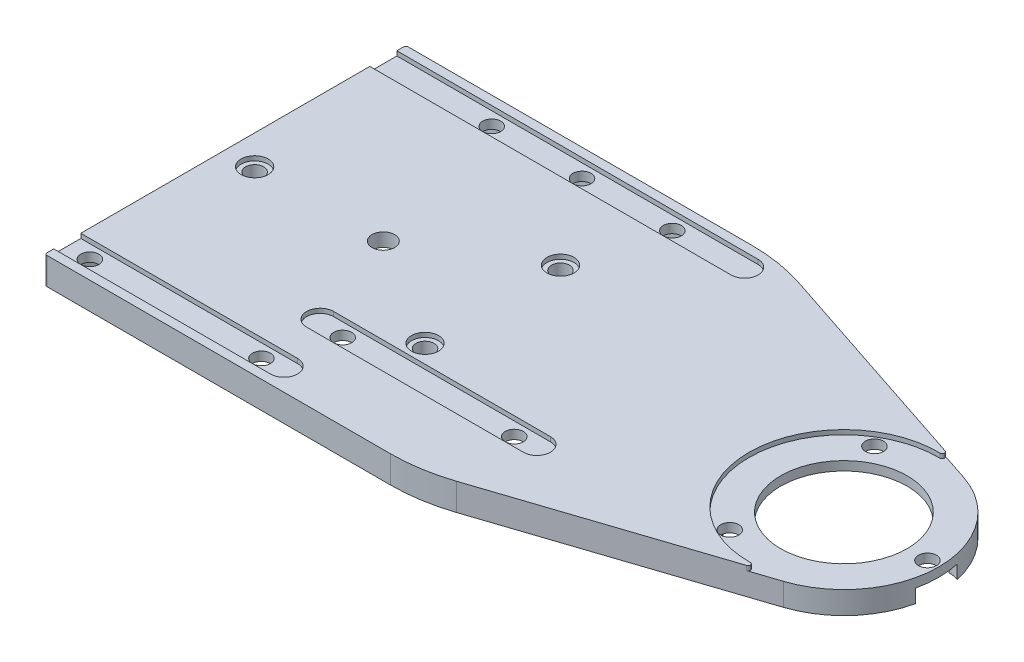
SolidWorks part; units mm, degrees
ref_plane "前视基准面" through (0, 0, 0) normal (0, 0, 1) x (1, 0, 0)
ref_plane "上视基准面" through (0, 0, 0) normal (0, 1, 0) x (1, 0, 0)
ref_plane "右视基准面" through (0, 0, 0) normal (1, 0, 0) x (0, 0, -1)
sketch "草图1" plane through (0, 0, 0) normal (0, 1, 0) x (1, 0, 0)
  line L0 (-20.9942, 0) -> (181.0483, 0) construction
  line L1 (-13, 40) -> (70, 40)
  line L2 (-13, 40) -> (-13, -40)
  line L3 (-13, -40) -> (70, -40)
  line L4 (70, 40) -> (130.6005, 19.9357)
  line L5 (0, 42.5732) -> (0, -49.2392) construction
  line L6 (124, 16.3237) -> (124, -16.3237) construction
  line L7 (70, 40) -> (130.6005, 19.9357) construction
  line L8 (70, -40) -> (130.6005, -19.9357) construction
  line L9 (70, -40) -> (130.6005, -19.9357)
  arc A0 (130.6005, -19.9357) -> (130.6005, 19.9357) centre (124, 0) ccw construction
  arc A5 (130.6005, -19.9357) -> (130.6005, 19.9357) centre (124, 0) ccw
  dimension "D5" = 42
  dimension "D7" = 42
  dimension "D1" = 13
  dimension "D2" = 40
  dimension "D3" = 40
  dimension "D4" = 124
  dimension "D9" = 70
extrude "凸台-拉伸1" add sketch "草图1" along normal blind 6
sketch "草图6" plane through (0, 6, 0) normal (0, 1, 0) x (1, 0, 0)
  line L1 (0, 0) -> (30.2712, 0) construction
  line L2 (30.2712, 0) -> (217.7288, 0) construction
  circle A0 centre (124, 0) radius 14
  dimension "D1" = 28
  dimension "D2" = 124
extrude "切除-拉伸4" cut sketch "草图6" against normal blind 10
sketch "草图7" plane through (0, 6, 0) normal (0, 1, 0) x (1, 0, 0)
  line L0 (11, 35) -> (51, 35) construction
  line L1 (0, 42.5732) -> (0, -49.2392) construction
  line L2 (-13, 40) -> (70, 40) construction
  circle A0 centre (11, 35) radius 2
  circle A1 centre (31, 35) radius 2
  circle A2 centre (51, 35) radius 2
  dimension "D1" = 4
  dimension "D2" = 11
  dimension "D3" = 5
  dimension "D4" = 20
extrude "切除-拉伸5" cut sketch "草图7" against normal blind 10
sketch "草图10" plane through (0, 6, 0) normal (0, 1, 0) x (1, 0, 0)
  line L0 (0, 0) -> (109.8479, 0) construction
  line L1 (11, 58) -> (11, -10.8563) construction
  line L2 (14, 58) -> (8, 58) construction
  line L3 (22, 0) -> (92.9812, 0) construction
  line L4 (-20.9942, 0) -> (181.0483, 0) construction
  line L5 (-6.5, 0) -> (46.2332, -15) construction
  circle A0 centre (22, 0) radius 2.5
  circle A1 centre (22, 0) radius 28.5 construction
  circle A2 centre (-6.5, 0) radius 2
  circle A3 centre (-6.5, 0) radius 3 construction
  circle A5 centre (46.2332, 15) radius 2
  circle A6 centre (46.2332, -15) radius 2
  circle A7 centre (46.2332, 15) radius 3 construction
  circle A8 centre (46.2332, -15) radius 3 construction
  dimension "D2" = 57
  dimension "D4" = 4
  dimension "D6" = 6
  dimension "D9" = 4
  dimension "D10" = 6
  dimension "D11" = 4
  dimension "D12" = 6
  dimension "D7" = 5
  dimension "D3" = 11
  dimension "D5" = 0
  dimension "D13" = 30
extrude "切除-拉伸7" cut sketch "草图10" against normal blind 10
sketch "草图11" plane through (0, 6, 0) normal (0, 1, 0) x (1, 0, 0)
  line L1 (-13, 38) -> (67, 38)
  line L2 (-13, 38) -> (-13, 32)
  line L3 (-13, 32) -> (67, 32)
  line L4 (67, 38) -> (67, 32) construction
  line L6 (70, 40) -> (-13, 40) construction
  line L7 (-13, 40) -> (-13, -40) construction
  arc A0 (67, 32) -> (67, 38) centre (67, 35) ccw
  dimension "D1" = 80
  dimension "D3" = 6
  dimension "D4" = 2
extrude "切除-拉伸8" cut sketch "草图11" against normal blind 1
sketch "草图13" plane through (0, 6, 0) normal (0, 1, 0) x (1, 0, 0)
  line L1 (-13, -38) -> (35, -38)
  line L2 (-13, -38) -> (-13, -32)
  line L3 (-13, -32) -> (35, -32)
  line L4 (35, -38) -> (35, -32) construction
  line L6 (-13, -40) -> (70, -40) construction
  line L7 (-13, 40) -> (-13, -40) construction
  arc A0 (35, -38) -> (35, -32) centre (35, -35) ccw
  dimension "D4" = 3
  dimension "D1" = 6
  dimension "D2" = 2
  dimension "D3" = 48
extrude "切除-拉伸9" cut sketch "草图13" against normal blind 1
sketch "草图14" plane through (0, 6, 0) normal (0, 1, 0) x (1, 0, 0)
  line L0 (-13, -40) -> (70, -40) construction
  line L1 (78, -25) -> (30, -25)
  line L2 (78, -25) -> (78, -19) construction
  line L3 (78, -19) -> (30, -19)
  line L4 (30, -25) -> (30, -19) construction
  line L5 (-13, 40) -> (-13, -40) construction
  arc A0 (78, -25) -> (78, -19) centre (78, -22) ccw
  arc A1 (30, -19) -> (30, -25) centre (30, -22) ccw
  dimension "D1" = 15
  dimension "D2" = 6
  dimension "D3" = 43
  dimension "D4" = 48
extrude "切除-拉伸10" cut sketch "草图14" against normal blind 1
sketch "草图16" plane through (0, 6, 0) normal (0, 1, 0) x (1, 0, 0)
  circle A0 centre (124, 0) radius 18.5 construction
  circle A1 centre (142.5, 0) radius 2
  circle A3 centre (114.75, -16.0215) radius 2
  circle A4 centre (114.75, 16.0215) radius 2
  point P12 (124, 0)
  dimension "D1" = 37
  dimension "D2" = 4
  dimension "D3" = 3
extrude "切除-拉伸11" cut sketch "草图16" against normal blind 10
sketch "草图17" plane through (0, 6, 0) normal (0, 1, 0) x (1, 0, 0)
  circle A0 centre (-8, -35) radius 2
  circle A1 centre (30, -35) radius 2
  circle A2 centre (35, -22) radius 2
  circle A3 centre (73, -22) radius 2
  dimension "D1" = 4
extrude "切除-拉伸12" cut sketch "草图17" against normal blind 10
sketch "草图18" plane through (0, 0, 0) normal (0, -1, 0) x (-1, 0, 0)
  line L0 (20.9942, 0) -> (-181.0483, 0) construction
  line L1 (11, 38) -> (-19, 38)
  line L2 (11, 38) -> (11, -1)
  line L4 (-19, 38) -> (-19, 19.2678)
  line L5 (13, -40) -> (-70, -40) construction
  line L6 (11, -38) -> (-19, -38)
  line L7 (11, -38) -> (11, -1)
  line L9 (-19, -38) -> (-19, -19.2678)
  line L10 (13, 40) -> (13, -40) construction
  line L11 (13, 40) -> (-70, 40) construction
  line L12 (-57, -38) -> (-69.6775, -38)
  line L13 (-21, 38) -> (-55, 38)
  line L14 (-21, 38) -> (-21, 19.4743)
  line L16 (-55, 38) -> (-55, 1)
  line L17 (-55, -38) -> (-21, -38)
  line L18 (-55, -38) -> (-55, -1)
  line L19 (-55, -1) -> (-41.4743, -1)
  line L20 (-21, -38) -> (-21, -19.4743)
  line L21 (-69.6775, -38) -> (-129.9719, -18.0371)
  line L22 (-70, 40) -> (-130.6005, 19.9357) construction
  line L23 (-55, 1) -> (-41.4743, 1)
  line L24 (-57, -13.5) -> (-57, -38)
  line L26 (-57, -11.5) -> (-106.4287, -11.5)
  line L27 (-57, -11.5) -> (-57, 11.5)
  line L28 (-57, 11.5) -> (-106.4287, 11.5)
  line L29 (-110.6303, -13.5) -> (-57, -13.5)
  line L30 (-124, 0) -> (-83.5288, 0) construction
  line L31 (-70, -40) -> (-93.8395, -32.1069) construction
  line L32 (-70, -40) -> (-130.6005, -19.9357) construction
  line L34 (-57, 13.5) -> (-57, 38)
  line L35 (-57, 38) -> (-69.6775, 38)
  line L36 (-69.6775, 38) -> (-129.9719, 18.0371)
  line L37 (-110.6303, 13.5) -> (-57, 13.5)
  circle A0 centre (-22, 0) radius 17.5
  arc A1 (-2.59, 1.8715) -> (-19, 19.2678) centre (-22, 0) ccw
  arc A2 (-106.4287, -11.5) -> (-106.4287, 11.5) centre (-124, 0) ccw
  arc A3 (-21, 19.4743) -> (-41.4743, 1) centre (-22, 0) ccw
  arc A4 (-41.4743, -1) -> (-21, -19.4743) centre (-22, 0) ccw
  arc A5 (-19, -19.2678) -> (-2.59, 1.8715) centre (-22, 0) ccw
  arc A7 (-129.9719, -18.0371) -> (-110.6303, -13.5) centre (-124, 0) ccw
  arc A8 (-110.6303, 13.5) -> (-129.9719, 18.0371) centre (-124, 0) ccw
  dimension "D2" = 35
  dimension "D3" = 39
  dimension "D26" = 42
  dimension "D30" = 2
  dimension "D1" = 22
  dimension "D4" = 2
  dimension "D7" = 2
  dimension "D8" = 2
  dimension "D10" = 30
  dimension "D11" = 30
  dimension "D12" = 2
  dimension "D13" = 2
  dimension "D14" = 2
  dimension "D15" = 2
  dimension "D16" = 2
  dimension "D17" = 1
  dimension "D18" = 34
  dimension "D19" = 34
  dimension "D20" = 2
  dimension "D21" = 2
  dimension "D22" = 4
  dimension "D23" = 23
  dimension "D24" = 2
  dimension "D25" = 2
  dimension "D31" = 2
extrude "切除-拉伸13" cut sketch "草图18" against normal blind 3
fillet "圆角1" radius 4 2 edges at (57, 1.5, 11.5) (57, 1.5, -11.5)
fillet "圆角2" radius 4 12 edges at (19, 1.5, -38) (-11, 1.5, -38) (21, 1.5, -38) (57, 1.5, -38) (57, 1.5, -13.5) (55, 1.5, -38) (55, 1.5, 1) (21, 1.5, 38) (55, 1.5, 38) (69.6775, 1.5, 38) (57, 1.5, 38) (57, 1.5, 13.5)
fillet "圆角3" radius 3 1 edges at (-11, 1.5, 38)
sketch "草图19" plane through (0, 0, 0) normal (0, -1, 0) x (1, 0, 0)
  circle A0 centre (114.75, 16.0215) radius 5
  circle A1 centre (142.5, 0) radius 5
  circle A2 centre (114.75, -16.0215) radius 5
  dimension "D1" = 10
extrude "切除-拉伸14" cut sketch "草图19" against normal blind 3
sketch "草图20" plane through (0, 0, 0) normal (0, -1, 0) x (1, 0, 0)
  circle A0 centre (124, 0) radius 14
  circle A1 centre (124, 0) radius 19
  dimension "D1" = 38
  dimension "D2" = 28
extrude "切除-拉伸15" cut sketch "草图20" against normal blind 3
sketch "草图21" plane through (0, 6, 0) normal (0, 1, 0) x (1, 0, 0)
  circle A0 centre (-6.5, 0) radius 3
  circle A1 centre (46.2332, 15) radius 3
  circle A2 centre (46.2332, -15) radius 3
  dimension "D1" = 6
  dimension "D2" = 6
  dimension "D3" = 6
extrude "切除-拉伸16" cut sketch "草图21" against normal blind 1
sketch "草图22" plane through (0, 3, 0) normal (0, -1, 0) x (1, 0, 0)
  circle A0 centre (46.2332, 15) radius 2
  circle A1 centre (46.2332, 15) radius 5
  circle A2 centre (46.2332, -15) radius 2
  circle A3 centre (46.2332, -15) radius 5
  circle A4 centre (-6.5, 0) radius 2
  circle A5 centre (-6.5, 0) radius 5
  dimension "D1" = 10
  dimension "D2" = 10
  dimension "D3" = 10
extrude "凸台-拉伸2" add sketch "草图22" along normal blind 3
fillet "圆角6" radius 4 1 edges at (19, 1.5, 38)
fillet "圆角7" radius 4 1 edges at (55, 1.5, -1)
fillet "圆角8" radius 0.5 2 edges at (-13, 3, -40) (-13, 3, 40)
fillet "圆角9" radius 40 2 edges at (70, 3, 40) (70, 3, -40)
fillet "圆角10" radius 4 6 edges at (21, 1.5, 19.4743) (19, 1.5, 19.2678) (19, 1.5, -19.2678) (21, 1.5, -19.4743) (41.4743, 1.5, -1) (41.4743, 1.5, 1)
fillet "圆角11" radius 3 2 edges at (106.4287, 1.5, 11.5) (106.4287, 1.5, -11.5)
fillet "圆角12" radius 4 1 edges at (69.6775, 1.5, -38)
fillet "圆角13" radius 3 2 edges at (-11, 1.5, -2.1794) (-11, 1.5, 2.1794)
sketch "草图23" plane through (0, 6, 0) normal (0, 1, 0) x (1, 0, 0)
  circle A0 centre (124, 0) radius 21
  dimension "D1" = 42
extrude "切除-拉伸17" cut sketch "草图23" against normal blind 1
fillet "圆角14" radius 0.5 2 edges at (130.6005, 5.5, 19.9357) (130.6005, 5.5, -19.9357)
sketch "草图24" plane through (0, 3, 0) normal (0, -1, 0) x (1, 0, 0)
  line L0 (-6.5, 0) -> (9.7491, 0) construction
  line L1 (22, 0) -> (46.2332, 15) construction
  line L2 (46.2332, 15) -> (60.0619, 15) construction
  line L3 (-1.5251, 0.5) -> (2.5064, 0.5)
  line L4 (-1.5251, -0.5) -> (2.5064, -0.5)
  line L5 (38.312, 10.6849) -> (41.7399, 12.8068)
  line L6 (42.2663, 11.9565) -> (38.8383, 9.8346)
  line L7 (51.2082, 14.5) -> (55, 14.5)
  line L8 (55, 14.5) -> (55, 15.5)
  line L9 (55, 15.5) -> (51.2082, 15.5)
  line L10 (55, 5) -> (55, 34) construction
  arc A0 (-1.5251, -0.5) -> (-1.5251, 0.5) centre (-6.5, 0) ccw
  arc A1 (38.8383, 9.8346) -> (38.312, 10.6849) centre (22, 0) ccw
  arc A2 (51.2082, 14.5) -> (51.2082, 15.5) centre (46.2332, 15) ccw
  arc A3 (2.5064, 0.5) -> (2.5064, -0.5) centre (22, 0) ccw
  arc A4 (41.7399, 12.8068) -> (42.2663, 11.9565) centre (46.2332, 15) ccw
  dimension "D4" = 10
  dimension "D5" = 39
  dimension "D6" = 10
  dimension "D1" = 1
  dimension "D2" = 1
  dimension "D3" = 1
extrude "凸台-拉伸3" add sketch "草图24" along normal blind 3
fillet "圆角15" radius 3 12 edges at (38.312, 1.5, 10.6849) (41.7399, 1.5, 12.8068) (55, 1.5, 15.5) (51.2082, 1.5, 15.5) (55, 1.5, 14.5) (51.2082, 1.5, 14.5) (38.8383, 1.5, 9.8346) (42.2663, 1.5, 11.9565) (2.5064, 1.5, 0.5) (-1.5251, 1.5, 0.5) (2.5064, 1.5, -0.5) (-1.5251, 1.5, -0.5)
mirror "镜向2" about plane through (0, 0, 0) normal (0, 0, 1) of "凸台-拉伸3"
fillet "圆角16" radius 3 8 edges at (38.8383, 1.5, -9.8346) (42.2663, 1.5, -11.9565) (55, 1.5, -14.5) (51.2082, 1.5, -14.5) (55, 1.5, -15.5) (51.2082, 1.5, -15.5) (41.7399, 1.5, -12.8068) (38.312, 1.5, -10.6849)
